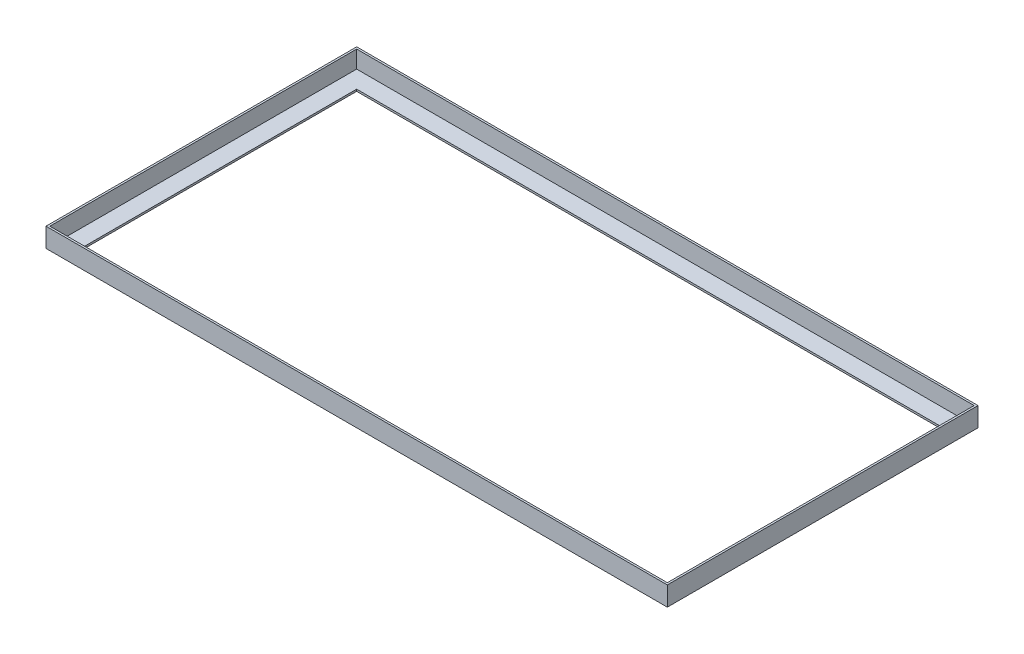
SolidWorks part; units mm, degrees
material "1.0037 (S235JR)"
ref_plane "Спереди" through (0, 0, 0) normal (0, 0, 1) x (1, 0, 0)
ref_plane "Сверху" through (0, 0, 0) normal (0, 1, 0) x (1, 0, 0)
ref_plane "Справа" through (0, 0, 0) normal (1, 0, 0) x (0, 0, -1)
sketch "Эскиз1" plane through (0, 0, 0) normal (0, 1, 0) x (1, 0, 0)
  line L1 (-111.8182, 726.656) -> (1498.1818, 726.656)
  line L2 (-111.8182, 726.656) -> (-111.8182, -78.344)
  line L3 (-111.8182, -78.344) -> (1498.1818, -78.344)
  line L4 (1498.1818, 726.656) -> (1498.1818, -78.344)
  line L5 (-106.8182, 721.656) -> (1493.1818, 721.656)
  line L6 (-106.8182, 721.656) -> (-106.8182, -73.344)
  line L7 (-106.8182, -73.344) -> (1493.1818, -73.344)
  line L8 (1493.1818, 721.656) -> (1493.1818, -73.344)
  line L13 (-61.8182, 676.656) -> (1448.1818, 676.656)
  line L14 (-61.8182, 676.656) -> (-61.8182, -28.344)
  line L15 (-61.8182, -28.344) -> (1448.1818, -28.344)
  line L16 (1448.1818, 676.656) -> (1448.1818, -28.344)
  dimension "D1" = 5
  dimension "D2" = 5
  dimension "D3" = 5
  dimension "D4" = 5
  dimension "D5" = 45
  dimension "D6" = 45
  dimension "D7" = 45
  dimension "D8" = 45
  dimension "D9" = 805
  dimension "D10" = 1610
extrude "Бобышка-Вытянуть1" add sketch "Эскиз1" along normal blind 50 contours L4 L1 L2 L3 L5 L8 L7 L6 region at (693.1818, 0, -724.856)
extrude "Бобышка-Вытянуть2" add sketch "Эскиз1<7>" along normal blind 5 contours L8 L5 L6 L7 L13 L16 L15 L14 region at (693.1818, 0, -703.7898)
sketch "Эскиз1<7>" plane through (0, 0, 0) normal (0, 1, 0) x (1, 0, 0) same geometry as "Эскиз1"
